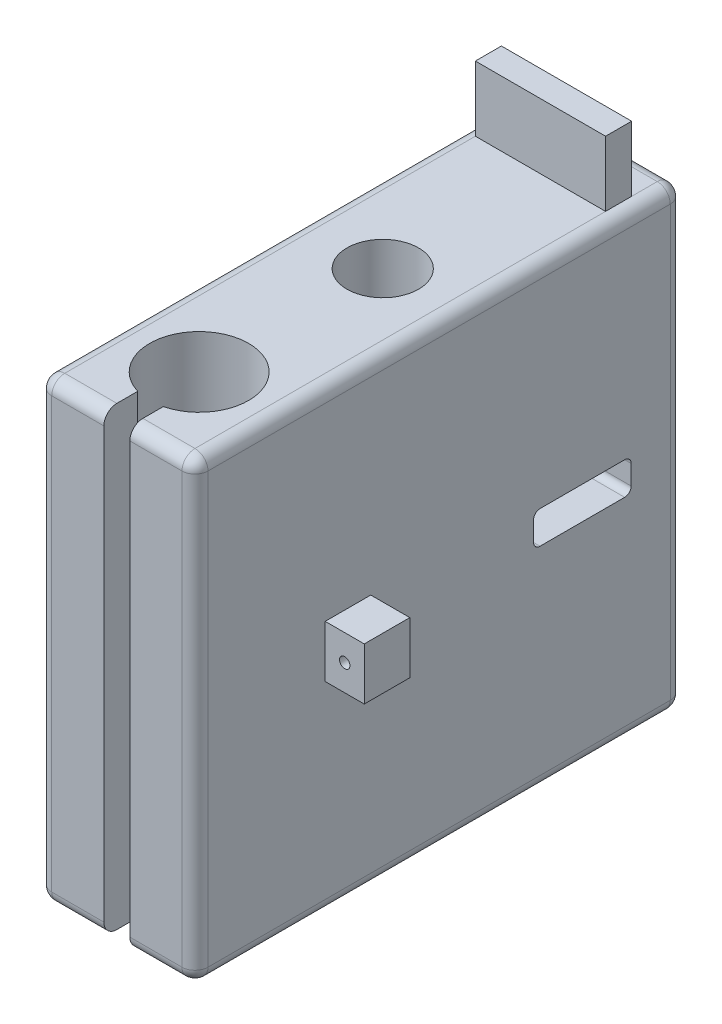
SolidWorks part; units mm, degrees
ref_plane "Front Plane" through (0, 0, 0) normal (0, 0, 1) x (1, 0, 0)
ref_plane "Top Plane" through (0, 0, 0) normal (0, 1, 0) x (1, 0, 0)
ref_plane "Right Plane" through (0, 0, 0) normal (1, 0, 0) x (0, 0, -1)
ref_plane "Plano1" through (-220, 0, 0) normal (1, 0, 0) x (0, 0, -1)
sketch "Esboço1" plane through (-220, 0, 0) normal (1, 0, 0) x (0, 0, -1)
  line L0 (-460.4999, 246.154) -> (-460.4999, 230.354) construction
  line L1 (-465.4999, 248.254) -> (-390.4999, 248.254)
  line L2 (-465.4999, 248.254) -> (-465.4999, 178.254)
  line L3 (-465.4999, 178.254) -> (-390.4999, 178.254)
  line L4 (-390.4999, 248.254) -> (-390.4999, 178.254)
  dimension "D1" = 75
  dimension "D2" = 70
  dimension "D3" = 5
extrude "Ressalto-extrusão1" add sketch "Esboço1" along normal blind 12 and the other way blind 12
sketch "Esboço3" plane through (0, 248.254, 0) normal (0, 1, 0) x (1, 0, 0)
  line L5 (-232, -465.4999) -> (-208, -465.4999) construction
  line L7 (-220, -465.4999) -> (-218, -465.4999)
  line L10 (-218, -465.4999) -> (-218, -460.3692)
  line L11 (-220, -465.4999) -> (-222, -465.4999)
  line L14 (-222, -465.4999) -> (-222, -460.292)
  arc A3 (-218, -460.3692) -> (-222, -460.292) centre (-219.8586, -452.9999) ccw
  circle A8 centre (-219.5085, -425.1499) radius 5.5
  circle A9 centre (-219.5085, -425.1499) radius 5.5
  dimension "D1" = 15.2
  dimension "D3" = 2
  dimension "D4" = 2
  dimension "D2" = 0.5
extrude "Corte-extrusão1" cut sketch "Esboço3" against normal through all
sketch "Esboço4" plane through (0, 0, 390.4999) normal (0, 0, -1) x (-1, 0, 0)
  line L0 (220, 248.254) -> (220, 178.254) construction
  line L1 (232, 248.254) -> (208, 248.254) construction
  line L2 (232, 178.254) -> (208, 178.254) construction
  circle A0 centre (219.8586, 238.254) radius 4.1
  circle A1 centre (219.8586, 188.254) radius 4.1
  dimension "D1" = 8.2
  dimension "D2" = 8.2
extrude "Corte-extrusão2" cut sketch "Esboço4" against normal blind 20
fillet "Filete1" radius 2 14 edges at (-227, 178.254, 465.4999) (-213, 178.254, 465.4999) (-213, 248.254, 465.4999) (-227, 248.254, 465.4999) (-208, 178.254, 427.9999) (-208, 248.254, 427.9999) (-208, 213.254, 465.4999) (-232, 178.254, 427.9999) (-232, 213.254, 465.4999) (-232, 248.254, 427.9999) (-220, 248.254, 390.4999) (-220, 178.254, 390.4999) (-208, 213.254, 390.4999) (-232, 213.254, 390.4999)
sketch "Esboço5" plane through (0, 0, 390.4999) normal (0, 0, -1) x (-1, 0, 0)
  line L8 (214.0179, 195.2585) -> (226.0179, 195.2487)
  line L9 (226.0179, 195.2487) -> (226.0474, 231.2487)
  line L10 (226.0474, 231.2487) -> (214.0474, 231.2585)
  line L11 (214.0474, 231.2585) -> (214.0179, 195.2585)
  line L12 (214.0179, 195.2585) -> (226.0179, 195.2487)
  line L13 (226.0179, 195.2487) -> (226.0474, 231.2487)
  line L14 (226.0474, 231.2487) -> (214.0474, 231.2585)
  line L15 (214.0474, 231.2585) -> (214.0179, 195.2585)
  dimension "D1" = 0
extrude "Corte-extrusão3" cut sketch "Esboço5" against normal blind 29
sketch "Esboço6" plane through (-232, 0, 0) normal (-1, 0, 0) x (0, 0, 1)
  line L0 (392.4999, 213.254) -> (463.4999, 213.254) construction
  line L1 (392.4999, 246.254) -> (392.4999, 180.254) construction
  line L2 (463.4999, 180.254) -> (463.4999, 246.254) construction
  line L3 (398.4999, 213.254) -> (413.4999, 213.254) construction
  line L4 (399.4999, 215.754) -> (412.4999, 215.754)
  line L5 (398.4999, 214.754) -> (398.4999, 211.754)
  line L6 (399.4999, 210.754) -> (412.4999, 210.754)
  line L7 (413.4999, 214.754) -> (413.4999, 211.754)
  arc A0 (412.4999, 215.754) -> (413.4999, 214.754) centre (412.4999, 214.754) cw
  arc A1 (412.4999, 210.754) -> (413.4999, 211.754) centre (412.4999, 211.754) ccw
  arc A2 (398.4999, 211.754) -> (399.4999, 210.754) centre (399.4999, 211.754) ccw
  arc A3 (399.4999, 215.754) -> (398.4999, 214.754) centre (399.4999, 214.754) ccw
  point P14 (413.4999, 215.754)
  point P17 (413.4999, 210.754)
  point P22 (398.4999, 215.754)
  dimension "D4" = 1
  dimension "D1" = 5
  dimension "D2" = 15
  dimension "D3" = 6
extrude "Corte-extrusão4" cut sketch "Esboço6" against normal blind 28
sketch "Esboço7" plane through (-208, 0, 0) normal (1, 0, 0) x (0, 0, -1)
  line L0 (-463.4999, 246.254) -> (-463.4999, 180.254) construction
  line L1 (-445.4999, 217.254) -> (-438.4999, 217.254)
  line L2 (-445.4999, 217.254) -> (-445.4999, 209.254)
  line L3 (-445.4999, 209.254) -> (-438.4999, 209.254)
  line L4 (-438.4999, 217.254) -> (-438.4999, 209.254)
  line L5 (-465.4999, 180.254) -> (-465.4999, 246.254) construction
  point P6 (-463.4999, 213.254)
  point P7 (-445.4999, 213.254)
  dimension "D1" = 7
  dimension "D2" = 8
  dimension "D3" = 20
extrude "Ressalto-extrusão2" add sketch "Esboço7" along normal blind 6 and the other way blind 30
ref_point "Ponto1"
sketch "Esboço9" plane through (0, 0, 445.4999) normal (0, 0, 1) x (1, 0, 0)
  line L0 (-205, 217.254) -> (-205, 209.254) construction
  line L3 (-208, 217.254) -> (-202, 217.254) construction
  line L6 (-208, 209.254) -> (-202, 209.254) construction
  line L7 (-208, 213.254) -> (-202, 213.254) construction
  line L8 (-208, 246.254) -> (-208, 180.254) construction
  line L9 (-202, 217.254) -> (-202, 209.254) construction
hole_wizard "Broca de rosquear para tarraxa de M2x0.41" positions "Esboço13" profile "Esboço14" hole size "M2x0.4" standard "Ansi Metric" end condition through all
sketch "Esboço13" plane through (0, 0, 445.4999) normal (0, 0, 1) x (1, 0, 0)
  line L0 (-205, 217.254) -> (-205, 209.254) construction
  point P0 (-205, 213.254)
sketch "Esboço14" plane through (-205, 213.254, 445.4999) normal (1, 0, 0) x (0, -1, 0)
  line L0 (0, 0) -> (0, 55)
  line L1 (0, 55) -> (0.8, 55)
  line L2 (0.8, 55) -> (0.8, 0)
  line L5 (0.8, 0) -> (0, 0)
  line L11 (0, -6.35) -> (0, 107.95) construction
  dimension "Thru Hole Dia." = 1.6
  dimension "Thru Hole Depth" = 55
sketch "Esboço15" plane through (0, 0, 445.4999) normal (0, 0, 1) x (1, 0, 0)
  line L0 (-235, 217.254) -> (-235, 209.254) construction
  line L1 (-238, 217.254) -> (-232, 217.254) construction
  line L2 (-238, 209.254) -> (-232, 209.254) construction
  line L3 (-238, 213.254) -> (-232, 213.254) construction
  line L4 (-238, 217.254) -> (-238, 209.254) construction
  line L5 (-232, 180.254) -> (-232, 246.254) construction
hole_wizard "Broca de rosquear para tarraxa de M2x0.42" positions "Esboço16" profile "Esboço17" hole size "M2x0.4" standard "Ansi Metric" end condition through all
sketch "Esboço16" plane through (0, 0, 445.4999) normal (0, 0, 1) x (1, 0, 0)
  line L0 (-235, 217.254) -> (-235, 209.254) construction
  point P0 (-235, 213.254)
sketch "Esboço17" plane through (-235, 213.254, 445.4999) normal (1, 0, 0) x (0, -1, 0)
  line L0 (0, 0) -> (0, 55)
  line L1 (0, 55) -> (0.8, 55)
  line L2 (0.8, 55) -> (0.8, 0)
  line L5 (0.8, 0) -> (0, 0)
  line L11 (0, -6.35) -> (0, 107.95) construction
  dimension "Thru Hole Dia." = 1.6
  dimension "Thru Hole Depth" = 55
sketch "Esboço18" plane through (0, 248.254, 0) normal (0, 1, 0) x (1, 0, 0)
  line L0 (-230, -392.4999) -> (-230, -463.4999) construction
  line L1 (-230, -396.4346) -> (-210, -396.4346)
  line L2 (-230, -396.4346) -> (-230, -400.4346)
  line L3 (-230, -400.4346) -> (-210, -400.4346)
  line L4 (-210, -396.4346) -> (-210, -400.4346)
  line L5 (-210, -463.4999) -> (-210, -392.4999) construction
  dimension "D1" = 4
extrude "Ressalto-extrusão3" add sketch "Esboço18" along normal blind 10
